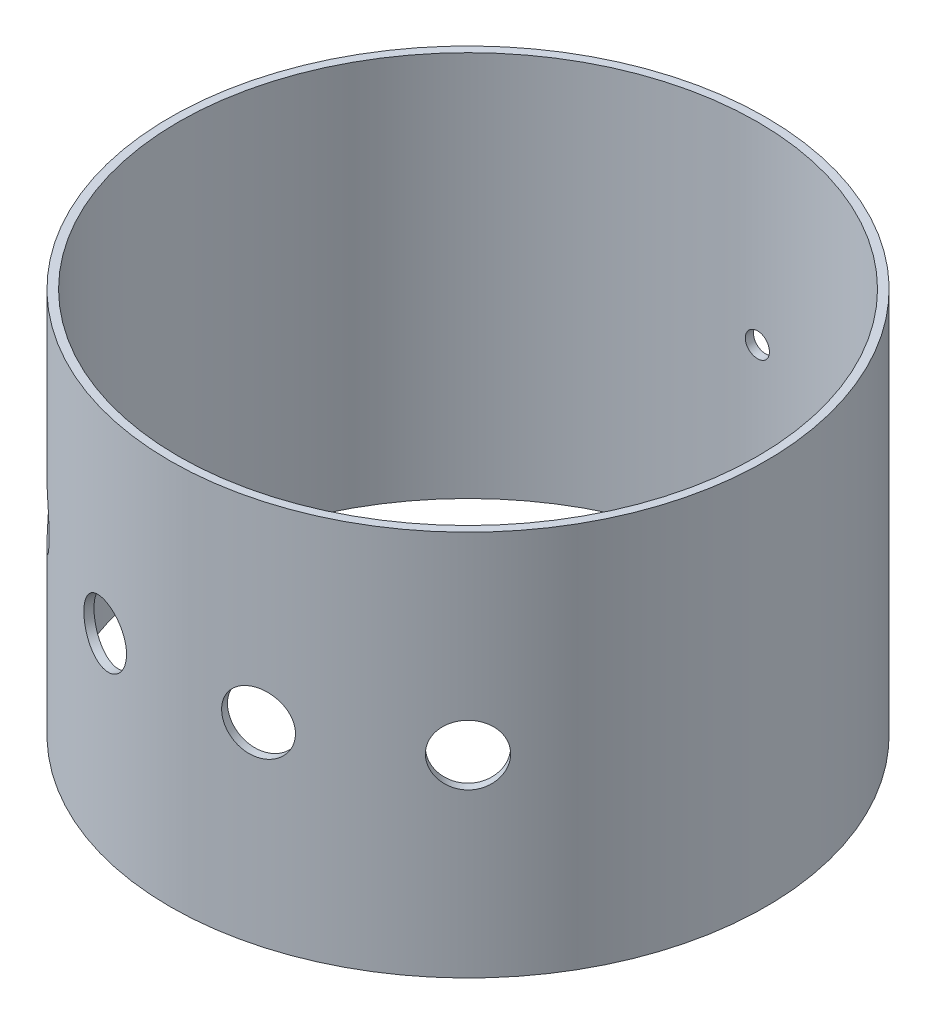
SolidWorks part; units mm, degrees
material "C-Glass Fiber"
ref_plane "Front Plane" through (0, 0, 0) normal (0, 0, 1) x (1, 0, 0)
ref_plane "Top Plane" through (0, 0, 0) normal (0, 1, 0) x (1, 0, 0)
ref_plane "Right Plane" through (0, 0, 0) normal (1, 0, 0) x (0, 0, -1)
sketch "Body Tube Profile" plane through (0, 0, 0) normal (0, 1, 0) x (1, 0, 0)
  circle A0 centre (0, 0) radius 76.2
  circle A1 centre (0, 0) radius 78.359
  dimension "D1" = 152.4
  dimension "D2" = 156.718
extrude "Body Tube Extrustion" add sketch "Body Tube Profile" along normal blind 101.6
sketch "Center Axis" plane through (0, 0, 0) normal (0, 0, 1) x (1, 0, 0)
  line L0 (0, 0) -> (0, 101.6) construction
  line L1 (76.2, 101.6) -> (-76.2, 101.6) construction
ref_plane "Offset Cut Plane" through (0, 0, 0) normal (0.7071, 0, 0.7071) x (0, 1, 0)
sketch "Sketch2" plane through (0, 0, 0) normal (0.7071, 0, 0.7071) x (0, 1, 0)
  line L0 (50.8, 78.359) -> (50.8, -78.359) construction
  line L1 (101.6, 78.359) -> (0, 78.359) construction
  line L2 (0, -78.359) -> (101.6, -78.359) construction
  circle A0 centre (50.8, 0) radius 7.9375
  dimension "D1" = 15.875
extrude "Key Hole Cut" cut sketch "Sketch2" along normal through all
pattern_circular "Key Hole Pattern" count 4 over 90 about axis through (0, 101.6, 0) along (0, 1, 0) of "Key Hole Cut" reverse direction yes
sketch "Sketch3" plane through (0, 0, 0) normal (0, 0, 1) x (1, 0, 0)
  line L0 (-78.359, 50.8) -> (78.359, 50.8) construction
  line L1 (-78.359, 101.6) -> (-78.359, 0) construction
  line L2 (78.359, 0) -> (78.359, 101.6) construction
  circle A0 centre (0, 50.8) radius 3.175
  dimension "D1" = 6.35
extrude "Cut-Extrude1" cut sketch "Sketch3" against normal through all
ref_plane "Plane1" through (0, 50.8, 0) normal (0, 1, 0) x (1, 0, 0)
sketch "Sketch5" plane through (0, 50.8, 0) normal (0, 1, 0) x (1, 0, 0)
  line L0 (0, 0) -> (0, 77.2795) construction
  line L1 (0, 0.0889) -> (85.8858, 0.0889)
  line L2 (0, 0.0889) -> (0, 0)
  line L3 (0, 0) -> (54.6449, -54.6449)
  line L4 (0, 0.1778) -> (0, -77.1017) construction
  dimension "D2" = 77.2795
  dimension "D3" = 45
equation "\"Length\"=4"
equation "\"Outer Diameter\"= 6.17"
equation "\"Inner Diameter\"= 6"
equation "\"Wall Thickness\"= 0.085"
equation "\"D1@Body Tube Profile\" = \"Inner Diameter\""
equation "\"D2@Body Tube Profile\" = \"Outer Diameter\""
equation "\"D1@Body Tube Extrustion\" = \"Length\""
equation "\"Key Hole Dia\"= 0.625"
equation "\"Hole Angle 1\"= 15"
equation "\"Hole Angle 2\"= 45"
equation "\"D1@Sketch2\"=\"Key Hole Dia\""
